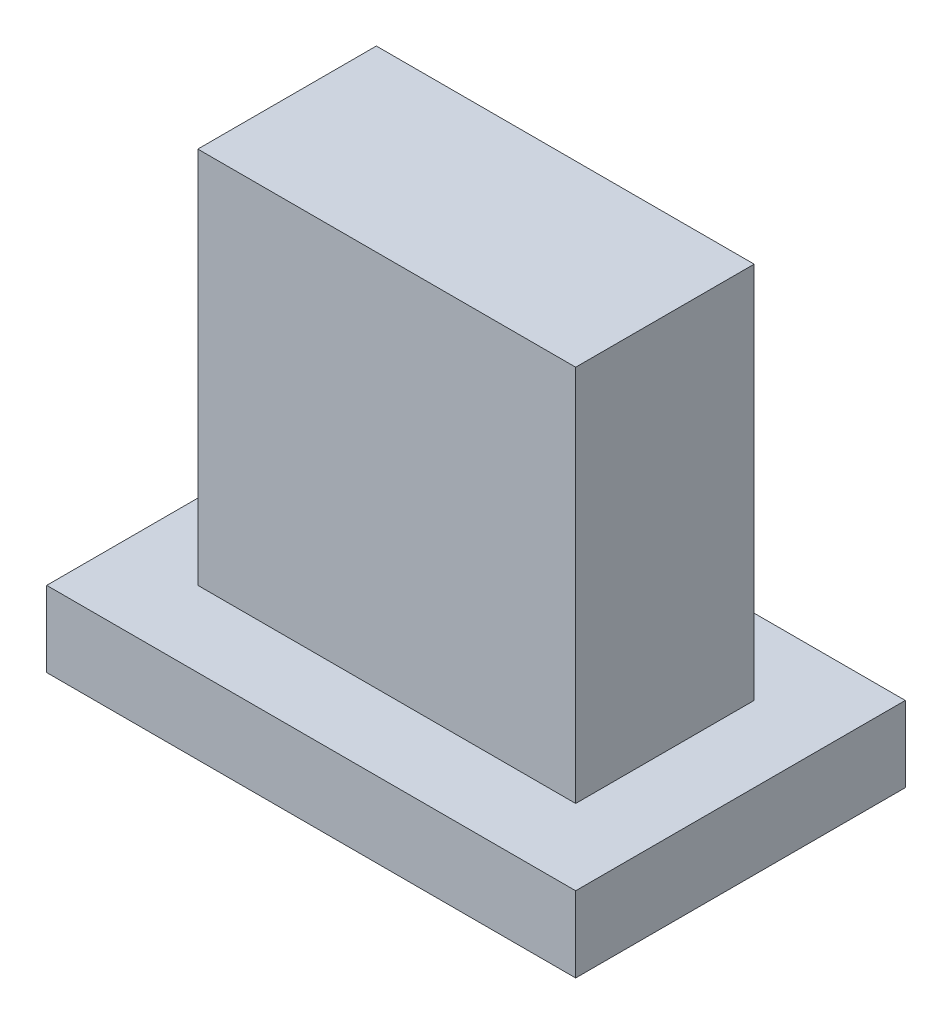
SolidWorks part; units mm, degrees
ref_plane "Front Plane" through (0, 0, 0) normal (0, 0, 1) x (1, 0, 0)
ref_plane "Top Plane" through (0, 0, 0) normal (0, 1, 0) x (1, 0, 0)
ref_plane "Right Plane" through (0, 0, 0) normal (1, 0, 0) x (0, 0, -1)
sketch "Sketch1" plane through (0, 0, 0) normal (0, 1, 0) x (1, 0, 0)
  line L0 (-8.89, 5.54) -> (8.89, 5.54)
  line L1 (-6.35, 3) -> (6.35, 3)
  line L2 (-6.35, 3) -> (-6.35, -3)
  line L3 (-6.35, -3) -> (6.35, -3)
  line L4 (6.35, 3) -> (6.35, -3)
  line L5 (8.89, 5.54) -> (8.89, -5.54)
  line L6 (-8.89, -5.54) -> (8.89, -5.54)
  line L7 (-8.89, 5.54) -> (-8.89, -5.54)
  point P4 (0, 3)
  point P6 (-6.35, 0)
  dimension "D1" = 6
  dimension "D2" = 12.7
  dimension "D3" = 2.54
extrude "Boss-Extrude1" add sketch "Sketch1" along normal blind 12.7 contours L4 L1 L2 L3 region at (0, 0, 0)
extrude "Boss-Extrude2" add sketch "Sketch1<3>" against normal blind 2.54 contours L4 L1 L2 L3 | L0 L7 L6 L5 L1 L4 L3 L2 region at (0, 0, -5.3305) region at (0, 0, 0)
sketch "Sketch1<3>" plane through (0, 0, 0) normal (0, 1, 0) x (1, 0, 0) same geometry as "Sketch1"
